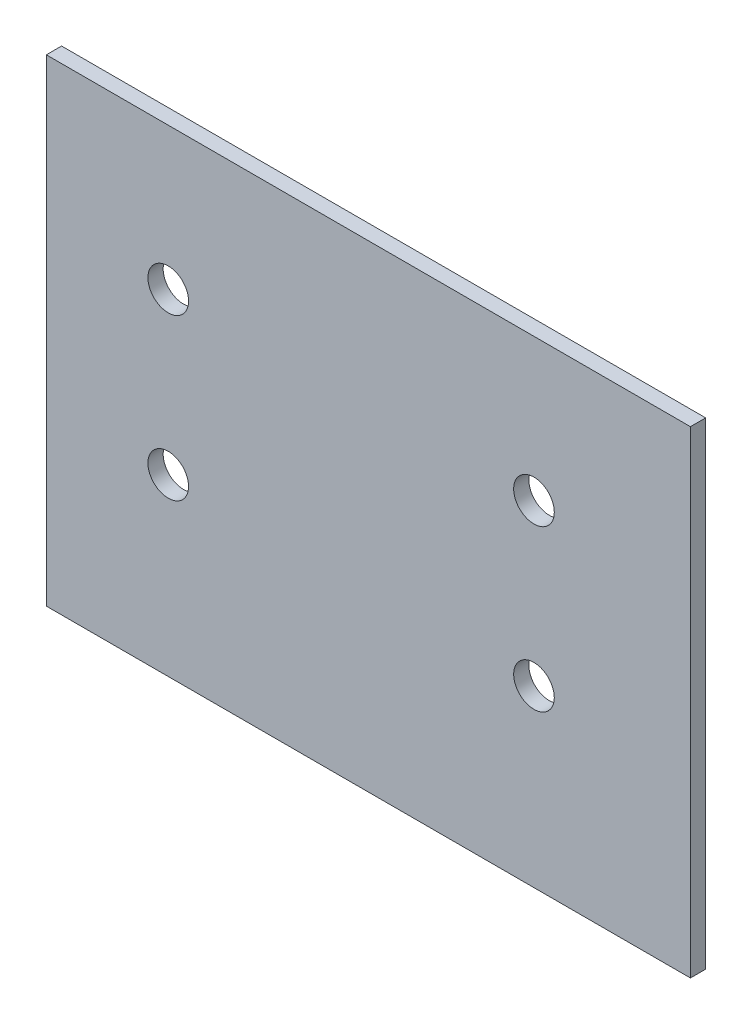
SolidWorks part; units mm, degrees
ref_plane "Front Plane" through (0, 0, 0) normal (0, 0, 1) x (1, 0, 0)
ref_plane "Top Plane" through (0, 0, 0) normal (0, 1, 0) x (1, 0, 0)
ref_plane "Right Plane" through (0, 0, 0) normal (1, 0, 0) x (0, 0, -1)
sketch "Sketch1" plane through (0, 0, 0) normal (0, 0, 1) x (1, 0, 0)
  line L1 (-40.259, 29.845) -> (40.259, 29.845)
  line L2 (-40.259, 29.845) -> (-40.259, -29.845)
  line L3 (-40.259, -29.845) -> (40.259, -29.845)
  line L4 (40.259, 29.845) -> (40.259, -29.845)
  line L5 (-40.259, 29.845) -> (40.259, -29.845) construction
  line L6 (-40.259, -29.845) -> (40.259, 29.845) construction
  point P0 (0, 0)
  dimension "D13" = 80.518
  dimension "D2" = 59.69
extrude "Boss-Extrude1" add sketch "Sketch1" along normal blind 1.905
sketch "Sketch2" plane through (0, 0, 1.905) normal (0, 0, 1) x (1, 0, 0)
  line L0 (40.259, 29.845) -> (-40.259, 29.845) construction
  line L1 (-40.259, 29.845) -> (-40.259, -29.845) construction
  circle A0 centre (-25.019, 12.065) radius 2.54
  circle A1 centre (-25.019, -8.001) radius 2.54
  circle A2 centre (20.701, 12.065) radius 2.54
  circle A3 centre (20.701, -8.001) radius 2.54
  dimension "D1" = 5.08
  dimension "D2" = 20.066
  dimension "D3" = 17.78
  dimension "D4" = 15.24
  dimension "D5" = 45.72
extrude "Cut-Extrude1" cut sketch "Sketch2" against normal through all
